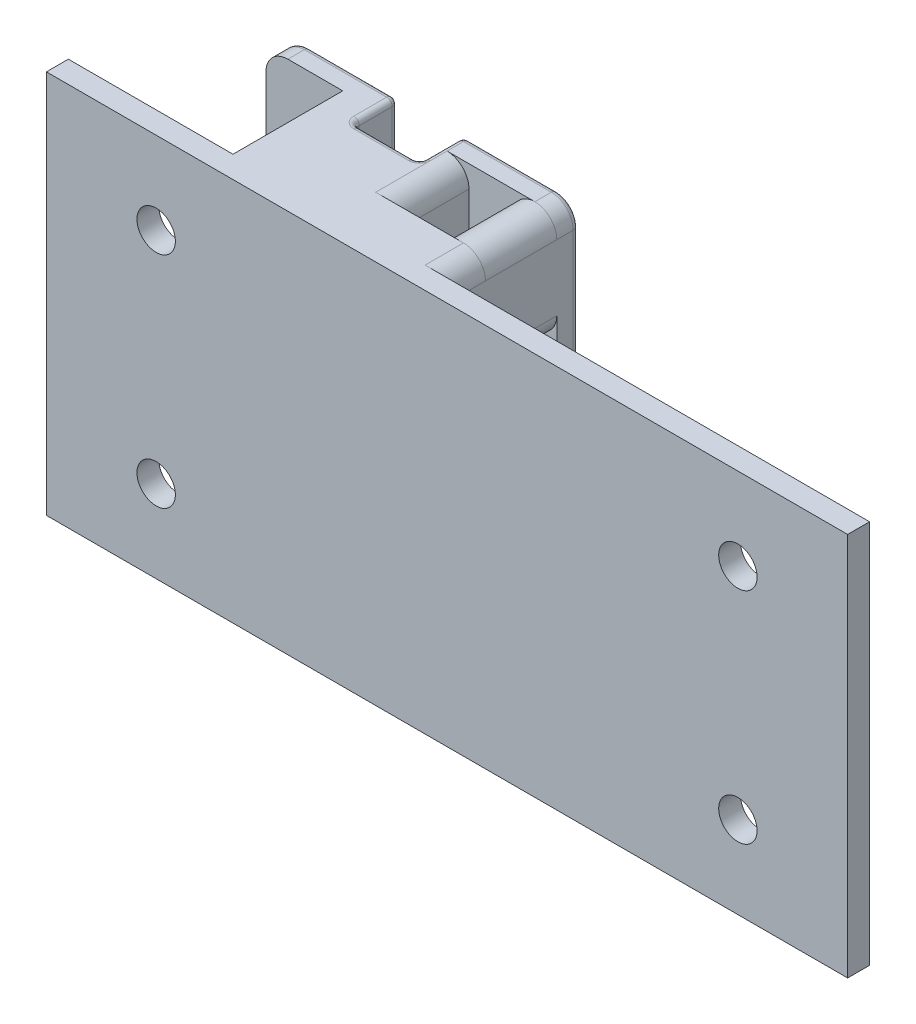
SolidWorks part; units mm, degrees
ref_plane "Plan de face" through (0, 0, 0) normal (0, 0, 1) x (1, 0, 0)
ref_plane "Plan de dessus" through (0, 0, 0) normal (0, 1, 0) x (1, 0, 0)
ref_plane "Plan de droite" through (0, 0, 0) normal (1, 0, 0) x (0, 0, -1)
sketch "Esquisse1" plane through (0, 0, 0) normal (0, 0, 1) x (1, 0, 0)
  line L0 (-36.5, 0) -> (-26.5, 0) construction
  line L1 (36.5, -17.5) -> (-36.5, -17.5)
  line L2 (36.5, -17.5) -> (36.5, 17.5)
  line L3 (36.5, 17.5) -> (-36.5, 17.5)
  line L4 (-36.5, -17.5) -> (-36.5, 17.5)
  line L8 (-26.5, 10) -> (-26.5, -10) construction
  line L9 (-23, 17.5) -> (-23, -17.5) construction
  line L10 (0, 17.5) -> (0, -17.5) construction
  circle A1 centre (-26.5, 10) radius 1.75
  circle A2 centre (-26.5, -10) radius 1.75
  circle A3 centre (26.5, -10) radius 1.75
  circle A4 centre (26.5, 10) radius 1.75
  point P18 (0, 0)
  dimension "D2" = 3.5
  dimension "D1" = 20
  dimension "D3" = 10
  dimension "D4" = 73
  dimension "D5" = 35
  dimension "D6" = 3.5
extrude "Boss.-Extru.1" add sketch "Esquisse1" against normal blind 2
sketch "Esquisse2" plane through (0, 0, -2) normal (0, 0, -1) x (-1, 0, 0)
  line L0 (4, 15.5) -> (4, 9.5) construction
  line L1 (6, 15.5) -> (6, 9.5)
  line L2 (2, 15.5) -> (2, 9.5)
  line L3 (-36.5, -17.5) -> (-36.5, 17.5) construction
  line L4 (-36.5, 0) -> (36.5, 0) construction
  line L5 (36.5, 17.5) -> (36.5, -17.5) construction
  line L6 (4, -15.5) -> (4, -9.5) construction
  line L7 (6, -15.5) -> (6, -9.5)
  line L8 (2, -15.5) -> (2, -9.5)
  line L9 (4, 9.5) -> (4, -9.5) construction
  line L10 (10, 17.5) -> (10, 5.5)
  line L11 (-36.5, 17.5) -> (36.5, 17.5) construction
  line L12 (10, 5.5) -> (2, 2.5)
  line L13 (2, 2.5) -> (2, -2.5)
  line L14 (2, -2.5) -> (10, -5.5)
  line L15 (10, -5.5) -> (10, -17.5)
  line L16 (36.5, -17.5) -> (-36.5, -17.5) construction
  line L17 (10, 17.5) -> (21.5, 17.5)
  line L18 (21.5, 17.5) -> (21.5, -17.5)
  line L19 (21.5, -17.5) -> (10, -17.5)
  arc A0 (6, 15.5) -> (2, 15.5) centre (4, 15.5) ccw
  arc A1 (2, 9.5) -> (6, 9.5) centre (4, 9.5) ccw
  arc A2 (6, -15.5) -> (2, -15.5) centre (4, -15.5) cw
  arc A3 (2, -9.5) -> (6, -9.5) centre (4, -9.5) cw
  point P2 (4, 12.5)
  point P15 (4, -12.5)
  point P27 (26.5, 10)
  point P37 (2, 0)
  dimension "D1" = 2
  dimension "D2" = 6
  dimension "D3" = 12.5
  dimension "D4" = 4
  dimension "D5" = 4
  dimension "D6" = 5
  dimension "D7" = 12
  dimension "D8" = 5
extrude "Boss.-Extru.2" add sketch "Esquisse2" along normal blind 10
sketch "Esquisse3" plane through (0, 0, -12) normal (0, 0, -1) x (-1, 0, 0)
  line L0 (0, 0) -> (2, 0) construction
  line L1 (2, 17.5) -> (28.5, 17.5)
  line L2 (2, 17.5) -> (2, -17.5)
  line L3 (2, -17.5) -> (28.5, -17.5)
  line L4 (28.5, 17.5) -> (28.5, -17.5)
  line L6 (2, 15.5) -> (2, 9.5) construction
  point P11 (26.5, 10)
  dimension "D1" = 2
  dimension "D2" = 35
extrude "Boss.-Extru.3" add sketch "Esquisse3" along normal blind 2
sketch "Esquisse4" plane through (0, 0, -2) normal (0, 0, -1) x (-1, 0, 0)
  line L0 (2, -17.5) -> (28.5, -17.5) construction
  line L1 (21.5, -17.5) -> (2, -17.5)
  line L2 (21.5, -17.5) -> (21.5, 17.5)
  line L3 (21.5, 17.5) -> (2, 17.5)
  line L4 (2, -17.5) -> (2, 17.5)
  line L5 (28.5, 17.5) -> (2, 17.5) construction
  line L6 (2, 15.5) -> (2, 9.5) construction
extrude "Boss.-Extru.4" add sketch "Esquisse4" along normal offset from surface (3.5 mm away) 6.5 up to face at (-5.7735, 10.8449, -12)
fillet "Congé1" radius 2 12 edges at (-2, -17.5, -13) (-2, 17.5, -13) (-10, -5.5, -8.75) (-10, 5.5, -8.75) (-2, -2.5, -8.75) (-2, 2.5, -8.75) (-10, -17.5, -8.75) (-10, 17.5, -8.75) (-2, -17.5, -3.75) (-2, 17.5, -3.75) (-28.5, -17.5, -13) (-28.5, 17.5, -13)
sketch "Esquisse5" plane through (0, 17.5, 0) normal (0, 1, 0) x (1, 0, 0)
  line L0 (-26.5, 14) -> (-4, 14) construction
  line L1 (-12.5, 14) -> (-18.5, 14)
  line L2 (-12.5, 14) -> (-12.5, 10)
  line L3 (-12.5, 10) -> (-18.5, 10)
  line L4 (-18.5, 14) -> (-18.5, 10)
  line L5 (-12, 5.5) -> (-12, 12) construction
  point P6 (-15.5, 14)
  dimension "D1" = 6
  dimension "D2" = 3.5
  dimension "D3" = 4
extrude "Enlèv. mat.-Extru.1" cut sketch "Esquisse5" against normal up to surface (35 mm away) up to face at (-9.7143, -17.5, -6.7857)
fillet "Congé2" radius 0.5 20 edges at (-18.5, -17.5, -12) (-12.5, -17.5, -12) (-15.5, -17.5, -10) (-12.5, 0, -10) (-18.5, 0, -10) (-12.5, 17.5, -12) (-15.5, 17.5, -10) (-18.5, 17.5, -12) (-8.25, -17.5, -14) (-2.5858, -16.9142, -14) (-2, 0, -14) (-2.5858, 16.9142, -14) (-8.25, 17.5, -14) (-12.5, 0, -14) (-18.5, 0, -14) (-22.5, -17.5, -14) (-27.9142, -16.9142, -14) (-28.5, 0, -14) (-27.9142, 16.9142, -14) (-22.5, 17.5, -14)
